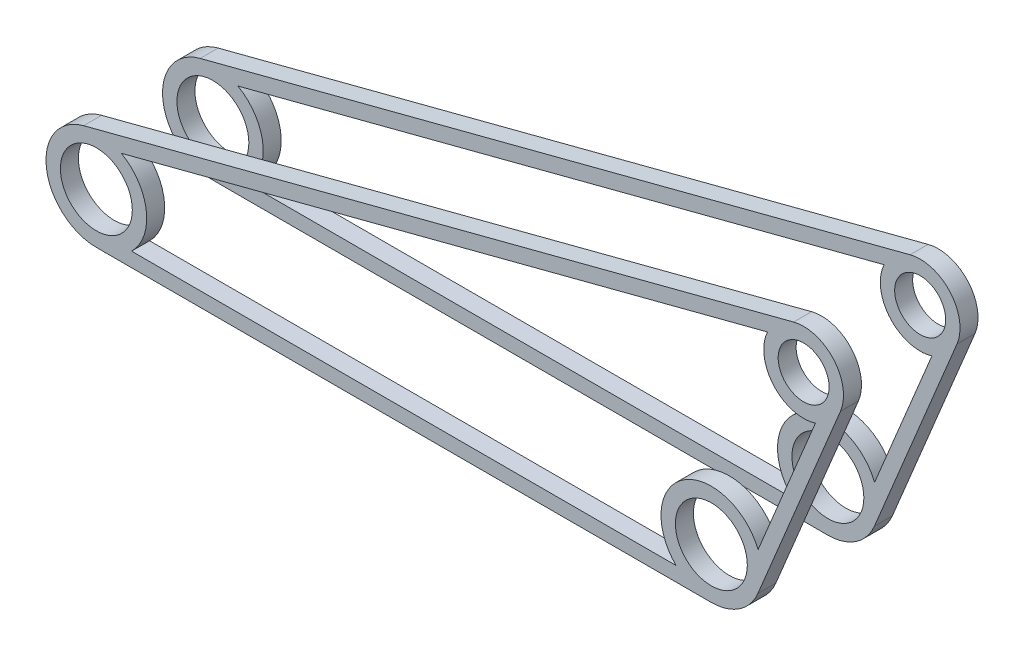
SolidWorks part; units mm, degrees
material "AISI 4130 Steel, annealed at 865C"
ref_plane "Front Plane" through (0, 0, 0) normal (0, 0, 1) x (1, 0, 0)
ref_plane "Top Plane" through (0, 0, 0) normal (0, 1, 0) x (1, 0, 0)
ref_plane "Right Plane" through (0, 0, 0) normal (1, 0, 0) x (0, 0, -1)
sketch "Sketch1" plane through (0, 0, 0) normal (0, 0, 1) x (1, 0, 0)
  line L0 (0, 0) -> (108.585, 0) construction
  line L1 (108.585, 0) -> (124.8778, 34.4406) construction
  line L2 (124.8778, 34.4406) -> (0, 0) construction
  line L3 (-2.2409, 8.6029) -> (123.1032, 41.2533)
  line L4 (131.3803, 31.7426) -> (116.7963, -3.407)
  line L5 (108.585, -8.89) -> (0, -8.89)
  line L6 (-1.6007, 6.1449) -> (123.7434, 38.7953)
  line L7 (0, -6.35) -> (108.585, -6.35)
  line L8 (114.4502, -2.4335) -> (129.0342, 32.7161)
  line L9 (111.596, -21.6868) -> (108.585, 0) construction
  circle A0 centre (0, 0) radius 6.35
  circle A1 centre (108.585, 0) radius 6.35
  circle A2 centre (124.8778, 34.4406) radius 4.5
  circle A3 centre (0, 0) radius 8.89
  circle A4 centre (108.585, 0) radius 8.89
  circle A5 centre (124.8778, 34.4406) radius 7.04
  dimension "D1" = 9
  dimension "D2" = 12.7
  dimension "D3" = 12.7
  dimension "D6" = 2.54
  dimension "D7" = 2.54
  dimension "D8" = 2.54
  dimension "D4" = 108.585
  dimension "D5" = 129.54
  dimension "D9" = 38.1
extrude "Boss-Extrude1" add sketch "Sketch1" along normal blind 3.175 from offset 8.6995 contours A5 L3 A3 L6 | L6 A3 L7 A0 | A4 L7 A3 L5 | L7 A4 L8 A1 | A5 L8 A4 L4 | A5 L6 A2 L8 | L7 A3 L6 A0 | L8 A4 L7 A1 | L6 A5 L8 A2 region at (1.146, 8.5805, 0) region at (60.9965, 23.7793, 0) region at (129.0654, 39.8588, 0) region at (54.2925, -7.6406, 0) region at (7.54, 4.3695, 0) region at (121.1641, 37.9583, 0) region at (105.2983, -8.0507, 0) region at (123.0705, 14.8619, 0) region at (103.7755, 7.2025, 0)
extrude "Boss-Extrude2" add sketch "Sketch1<4>" against normal blind 3.175 from offset 8.6995 separate body contours A5 L3 A3 L6 | L6 A3 L7 A0 | L7 A3 L6 A0 | A4 L7 A3 L5 | L7 A4 L8 A1 | L8 A4 L7 A1 | A5 L8 A4 L4 | L6 A5 L8 A2 | A5 L6 A2 L8 region at (1.146, 8.5805, 0) region at (60.9965, 23.7793, 0) region at (129.0654, 39.8588, 0) region at (54.2925, -7.6406, 0) region at (7.54, 4.3695, 0) region at (121.1641, 37.9583, 0) region at (105.2983, -8.0507, 0) region at (123.0705, 14.8619, 0) region at (103.7755, 7.2025, 0) offset against normal yes
sketch "Sketch1<4>" plane through (0, 0, 0) normal (0, 0, 1) x (1, 0, 0) same geometry as "Sketch1"
equation "\"D19@Boss-Extrude2\"=.45"
